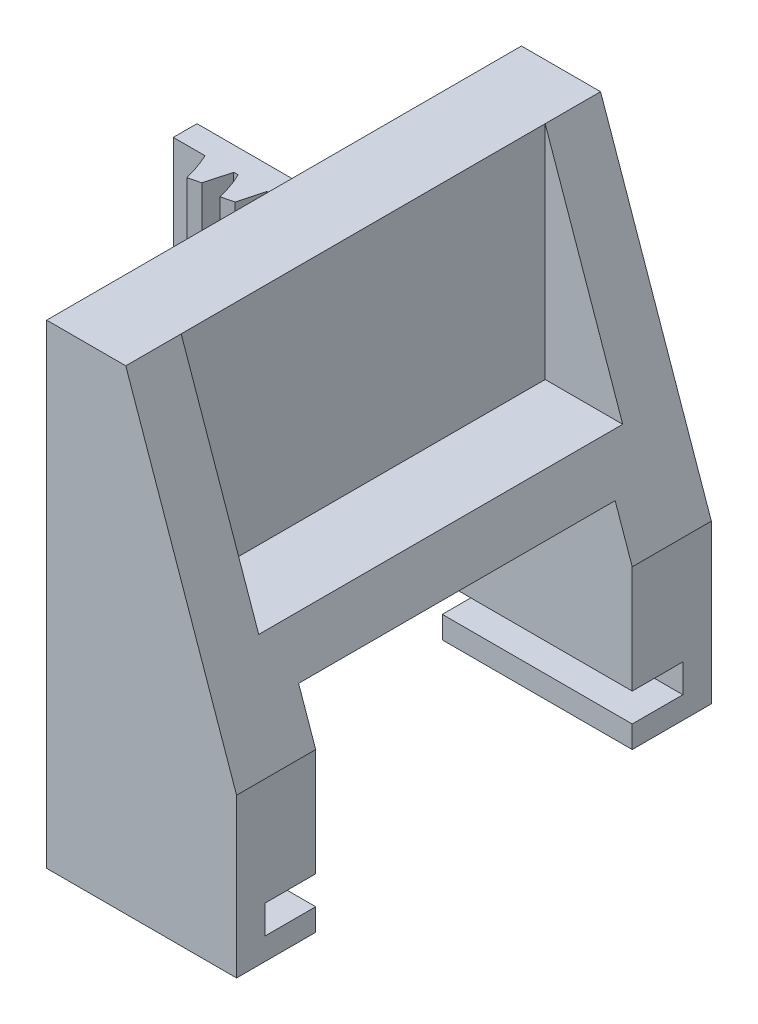
SolidWorks part; units mm, degrees
ref_plane "Front Plane" through (0, 0, 0) normal (0, 0, 1) x (1, 0, 0)
ref_plane "Top Plane" through (0, 0, 0) normal (0, 1, 0) x (1, 0, 0)
ref_plane "Right Plane" through (0, 0, 0) normal (1, 0, 0) x (0, 0, -1)
sketch "Sketch1" plane through (0, 0, 0) normal (0, 0, 1) x (1, 0, 0)
  line L0 (0, 0) -> (0, -30)
  line L1 (0, -30) -> (12, -30)
  line L2 (12, -30) -> (12, -20)
  line L3 (12, -20) -> (5, 0)
  line L4 (5, 0) -> (0, 0)
  dimension "D1" = 30
  dimension "D2" = 12
  dimension "D3" = 10
  dimension "D4" = 5
extrude "Boss-Extrude1" add sketch "Sketch1" against normal blind 30
sketch "Sketch4" plane through (0, 0, 0) normal (-1, 0, 0) x (0, 0, 1)
  line L0 (-30, 0) -> (-30, -30) construction
  line L1 (-25, -16.9179) -> (-5, -16.9179)
  line L2 (-25, -16.9179) -> (-25, -30.9179)
  line L3 (-25, -30.9179) -> (-5, -30.9179)
  line L4 (-5, -16.9179) -> (-5, -30.9179)
  point P4 (-25, -23.9179)
  dimension "D1" = 20
  dimension "D2" = 14
  dimension "D3" = 5
extrude "Cut-Extrude2" cut sketch "Sketch4" against normal blind 25 contours L2 L1 L4 L3
sketch "Sketch5" plane through (0, 0, 0) normal (-1, 0, 0) x (0, 0, 1)
  line L0 (-5, -16.9179) -> (-5, -30) construction
  line L1 (-5, -26.8) -> (-1.8, -26.8)
  line L2 (-5, -26.8) -> (-5, -28.6)
  line L3 (-5, -28.6) -> (-1.8, -28.6)
  line L4 (-1.8, -26.8) -> (-1.8, -28.6)
  line L5 (-5, -30) -> (0, -30) construction
  dimension "D1" = 1.8
  dimension "D2" = 3.2
  dimension "D3" = 1.4
extrude "Cut-Extrude3" cut sketch "Sketch5" against normal blind 15
ref_plane "Plane1" through (0, 0, -15) normal (0, 0, 1) x (1, 0, 0)
mirror "Mirror1" about plane through (0, 0, -15) normal (0, 0, 1) of "Cut-Extrude3"
sketch "Sketch6" plane through (0, 0, -15) normal (0, 0, 1) x (1, 0, 0)
  line L0 (5, 0) -> (5, -14)
  line L1 (5, -14) -> (9.9, -14)
  line L2 (12, -20) -> (5, 0) construction
  line L3 (9.9, -14) -> (5, 0)
  dimension "D1" = 14
extrude "Cut-Extrude4" cut sketch "Sketch6" against normal mid plane 23
ref_plane "Plane2" through (0, -21, 0) normal (0, 1, 0) x (1, 0, 0)
sketch "Sketch7" plane through (0, -21, 0) normal (0, 1, 0) x (1, 0, 0)
  line L0 (0, 28.5) -> (-19, 28.5)
  line L1 (0, 30) -> (0, 0) construction
  line L3 (0, 28.5) -> (0, 27)
  line L4 (0, 27) -> (-0.5, 27)
  line L47 (-0.5, 27) -> (-0.9304, 25.4151)
  line L62 (-6.6, 15) -> (6.6, 15) construction
  line L108 (-19, 27) -> (-19, 28.5)
  line L112 (-0.9304, 25.4151) -> (-1.6865, 25.2276)
  line L113 (-2.3144, 27) -> (-2.597, 27)
  line L114 (-3.0274, 25.4151) -> (-3.7835, 25.2276)
  line L115 (-2.597, 27) -> (-3.0274, 25.4151)
  line L116 (-5.1244, 25.4151) -> (-5.8805, 25.2276)
  line L117 (-4.694, 27) -> (-5.1244, 25.4151)
  line L118 (-7.2214, 25.4151) -> (-7.9775, 25.2276)
  line L119 (-6.791, 27) -> (-7.2214, 25.4151)
  line L120 (-9.3184, 25.4151) -> (-10.0745, 25.2276)
  line L121 (-8.888, 27) -> (-9.3184, 25.4151)
  line L122 (-11.4154, 25.4151) -> (-12.1715, 25.2276)
  line L123 (-10.985, 27) -> (-11.4154, 25.4151)
  line L124 (-13.5124, 25.4151) -> (-14.2685, 25.2276)
  line L125 (-13.082, 27) -> (-13.5124, 25.4151)
  line L126 (-4.4114, 27) -> (-4.694, 27)
  line L127 (-6.5085, 27) -> (-6.791, 27)
  line L128 (-8.6055, 27) -> (-8.888, 27)
  line L129 (-10.7025, 27) -> (-10.985, 27)
  line L130 (-12.7995, 27) -> (-13.082, 27)
  line L132 (-15.6094, 25.4151) -> (-16.3655, 25.2276)
  line L133 (-15.179, 27) -> (-15.6094, 25.4151)
  line L134 (-14.8965, 27) -> (-15.179, 27)
  line L135 (-16.9935, 27) -> (-19, 27)
  arc A0 (-1.6865, 25.2276) -> (-2.3144, 27) centre (-11.0716, 22.8998) ccw
  arc A1 (-3.7835, 25.2276) -> (-4.4114, 27) centre (-13.1686, 22.8998) ccw
  arc A2 (-5.8805, 25.2276) -> (-6.5085, 27) centre (-15.2656, 22.8998) ccw
  arc A3 (-7.9775, 25.2276) -> (-8.6055, 27) centre (-17.3626, 22.8998) ccw
  arc A4 (-10.0745, 25.2276) -> (-10.7025, 27) centre (-19.4596, 22.8998) ccw
  arc A5 (-12.1715, 25.2276) -> (-12.7995, 27) centre (-21.5566, 22.8998) ccw
  arc A6 (-14.2685, 25.2276) -> (-14.8965, 27) centre (-23.6536, 22.8998) ccw
  arc A7 (-16.3655, 25.2276) -> (-16.9935, 27) centre (-25.7506, 22.8998) ccw
  dimension "D1" = 7
  dimension "D4" = 8
  dimension "D2" = 19
  dimension "D3" = 1.5
  dimension "D6" = 0.5
  dimension "D7" = 13.5
extrude "Boss-Extrude2" add sketch "Sketch7" along normal blind 8
